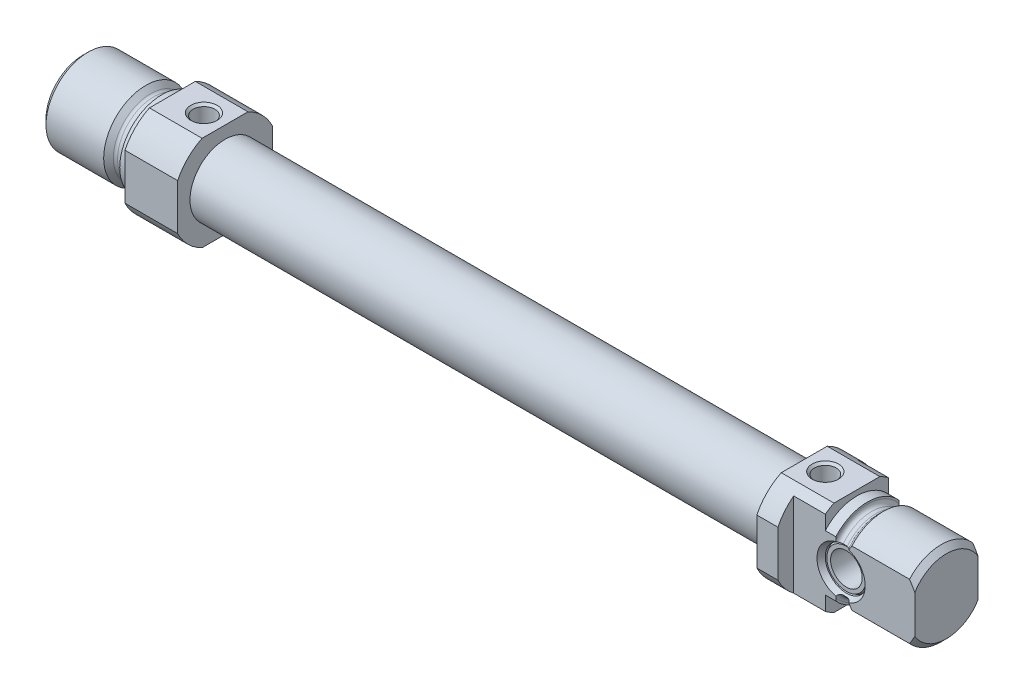
SolidWorks part; units mm, degrees
ref_plane "Front Plane" through (0, 0, 0) normal (0, 0, 1) x (1, 0, 0)
ref_plane "Top Plane" through (0, 0, 0) normal (0, 1, 0) x (1, 0, 0)
ref_plane "Right Plane" through (0, 0, 0) normal (1, 0, 0) x (0, 0, -1)
sketch "Sketch1" plane through (0, 0, 0) normal (0, 0, 1) x (1, 0, 0)
  line L0 (0, 0) -> (0, 7)
  line L1 (0, 7) -> (1, 8)
  line L2 (1, 8) -> (11.95, 8)
  line L3 (11.95, 8) -> (12.8657, 7.0843)
  line L4 (13.4314, 6.85) -> (14.2, 6.85)
  line L5 (15, 7.65) -> (15, 8)
  line L6 (15, 8) -> (17, 8)
  line L7 (17, 8) -> (17, 0)
  line L8 (17, 0) -> (0, 0)
  line L9 (17, 0) -> (0, 0) construction
  arc A0 (12.8657, 7.0843) -> (13.4314, 6.85) centre (13.4314, 7.65) ccw
  arc A1 (14.2, 6.85) -> (15, 7.65) centre (14.2, 7.65) ccw
revolve "Revolve1" add sketch "Sketch1" angle 360 about L9 reverse direction yes
cosmetic thread "Cosmetic Thread1" parameters "D1"=11.87, "D2"=14.16
ref_plane "Plane1" through (21.1, 0, 0) normal (1, 0, 0) x (0, 0, -1)
ref_plane "Plane2" through (9, 0, 0) normal (1, 0, 0) x (0, 0, -1)
ref_plane "Plane3" through (0, -11, 0) normal (0, 1, 0) x (1, 0, 0)
ref_plane "Plane4" through (0, 11, 0) normal (0, 1, 0) x (1, 0, 0)
ref_plane "Plane5" through (0, 0, 0) normal (0, 1, 0) x (1, 0, 0)
ref_plane "Plane6" through (0, 0, 0) normal (0, 1, 0) x (1, 0, 0)
ref_plane "Plane7" through (17, 0, 0) normal (1, 0, 0) x (0, 0, -1)
ref_plane "Plane8" through (17, 0, 0) normal (1, 0, 0) x (0, 0, -1)
ref_plane "Plane9" through (27, 0, 0) normal (1, 0, 0) x (0, 0, -1)
ref_plane "Plane10" through (17, 0, 0) normal (1, 0, 0) x (0, 0, -1)
ref_plane "Plane11" through (17, 0, 0) normal (1, 0, 0) x (0, 0, -1)
sketch "Sketch2" plane through (17, 0, 0) normal (1, 0, 0) x (0, 0, -1)
  line L0 (-4.3589, -9) -> (4.3589, -9)
  line L1 (9, -4.3589) -> (9, 4.3589)
  line L2 (4.3589, 9) -> (-4.3589, 9)
  line L3 (-9, 4.3589) -> (-9, -4.3589)
  arc A0 (-9, -4.3589) -> (-4.3589, -9) centre (0, 0) ccw
  arc A1 (4.3589, -9) -> (9, -4.3589) centre (0, 0) ccw
  arc A2 (9, 4.3589) -> (4.3589, 9) centre (0, 0) ccw
  arc A3 (-4.3589, 9) -> (-9, 4.3589) centre (0, 0) ccw
extrude "Boss-Extrude1" add sketch "Sketch2" along normal blind 10
ref_plane "Plane12" through (23, 0, 0) normal (1, 0, 0) x (0, 0, -1)
ref_plane "Plane13" through (0, 0, 0) normal (0, 0, 1) x (1, 0, 0)
ref_plane "Plane14" through (0, 0, -6.6) normal (0, 0, 1) x (1, 0, 0)
ref_plane "Plane15" through (0, 0, 0) normal (0, 1, 0) x (1, 0, 0)
ref_plane "Plane16" through (0, 7.5, 0) normal (0, 1, 0) x (1, 0, 0)
ref_plane "Plane17" through (0, 0, -6.6) normal (0, 0, 1) x (1, 0, 0)
ref_plane "Plane18" through (0, 0, 0) normal (0, 1, 0) x (1, 0, 0)
ref_plane "Plane19" through (0, 7.5, 0) normal (0, 1, 0) x (1, 0, 0)
ref_plane "Plane20" through (0, 8.4025, -1.4816) normal (0, 0.9848, -0.1736) x (1, 0, 0)
ref_plane "Plane21" through (0, 6.9253, -1.2211) normal (0, 0.9848, -0.1736) x (1, 0, 0)
sketch "Sketch3" plane through (0, 0, 0) normal (0, 0, 1) x (1, 0, 0)
  line L0 (27, 0) -> (27, 6.65)
  line L1 (27, 6.65) -> (137, 6.65)
  line L2 (137, 6.65) -> (137, 0)
  line L3 (137, 0) -> (27, 0)
  line L4 (137, 0) -> (27, 0) construction
revolve "Revolve2" add sketch "Sketch3" angle 360 about L4 reverse direction yes
ref_plane "Plane22" through (137, 0, 0) normal (1, 0, 0) x (0, 0, -1)
sketch "Sketch4" plane through (137, 0, 0) normal (1, 0, 0) x (0, 0, -1)
  line L0 (-9, -9) -> (9, -9)
  line L1 (9, -9) -> (9, 9)
  line L2 (9, 9) -> (-9, 9)
  line L3 (-9, 9) -> (-9, -9)
extrude "Boss-Extrude2" add sketch "Sketch4" along normal blind 10
sketch "Sketch5" plane through (0, 0, 0) normal (0, 0, 1) x (1, 0, 0)
  line L0 (137, 20) -> (137, 10)
  line L1 (137, 10) -> (147, 10)
  line L2 (147, 10) -> (147, 20)
  line L3 (147, 20) -> (137, 20)
  line L4 (147, 0) -> (137, 0) construction
revolve "Cut-Revolve1" cut sketch "Sketch5" angle 360 about L4 reverse direction yes
ref_plane "Plane23" through (139, 0, 0) normal (1, 0, 0) x (0, 0, -1)
ref_plane "Plane24" through (141, 0, 0) normal (1, 0, 0) x (0, 0, -1)
ref_plane "Plane25" through (0, 0, 6.6) normal (0, 0, 1) x (1, 0, 0)
ref_plane "Plane26" through (0, 0, 0) normal (0, 1, 0) x (1, 0, 0)
ref_plane "Plane27" through (0, 7.5, 0) normal (0, 1, 0) x (1, 0, 0)
ref_plane "Plane28" through (0, 8.4025, 1.4816) normal (0, 0.9848, 0.1736) x (1, 0, 0)
ref_plane "Plane29" through (0, 6.9253, 1.2211) normal (0, 0.9848, 0.1736) x (1, 0, 0)
ref_plane "Plane30" through (185, 0, 0) normal (1, 0, 0) x (0, 0, -1)
sketch "Sketch6" plane through (0, 0, 0) normal (0, 0, 1) x (1, 0, 0)
  line L0 (147, 0) -> (147, 8)
  line L1 (147, 8) -> (149, 8)
  line L2 (149, 8) -> (149, 7.65)
  line L3 (149.8, 6.85) -> (150.5686, 6.85)
  line L4 (151.1343, 7.0843) -> (152.05, 8)
  line L5 (152.05, 8) -> (163, 8)
  line L6 (163, 8) -> (164, 7)
  line L7 (164, 7) -> (164, 0)
  line L8 (164, 0) -> (147, 0)
  line L9 (164, 0) -> (147, 0) construction
  arc A0 (149, 7.65) -> (149.8, 6.85) centre (149.8, 7.65) ccw
  arc A1 (150.5686, 6.85) -> (151.1343, 7.0843) centre (150.5686, 7.65) ccw
revolve "Revolve3" add sketch "Sketch6" angle 360 about L9 reverse direction yes
cosmetic thread "Cosmetic Thread2" parameters "D1"=11.87, "D2"=14.16
ref_plane "Plane31" through (175, 0, 0) normal (1, 0, 0) x (0, 0, -1)
ref_plane "Plane32" through (185, 0, 0) normal (1, 0, 0) x (0, 0, -1)
ref_plane "Plane33" through (185, 0, 0) normal (1, 0, 0) x (0, 0, -1)
sketch "Sketch7" plane through (0, 0, 0) normal (0, 1, 0) x (1, 0, 0)
  line L0 (141, 18) -> (141, 6)
  line L1 (141, 6) -> (164, 6)
  line L2 (164, 6) -> (164, -6)
  line L3 (164, -6) -> (141, -6)
  line L4 (141, -6) -> (141, -18)
  line L5 (141, -18) -> (176, -18)
  line L6 (176, -18) -> (176, 18)
  line L7 (176, 18) -> (141, 18)
extrude "Cut-Extrude1" cut sketch "Sketch7" along normal blind 10 and the other way blind 10
ref_plane "Plane34" through (150, 0, 0) normal (1, 0, 0) x (0, 0, -1)
sketch "Sketch8" plane through (150, 0, 0) normal (1, 0, 0) x (0, 0, -1)
  line L0 (-6.2, 0) -> (-6.2, 4.6928)
  line L1 (-6.2, 4.6928) -> (-5, 4)
  line L2 (-5, 4) -> (-4.5, 4)
  line L3 (-4.5, 4) -> (-5, 3.7113)
  line L4 (-5, 3.7113) -> (-5, 3)
  line L5 (-5, 3) -> (5, 3)
  line L6 (5, 3) -> (5, 3.7113)
  line L7 (5, 3.7113) -> (4.5, 4)
  line L8 (4.5, 4) -> (5, 4)
  line L9 (5, 4) -> (6.2, 4.6928)
  line L10 (6.2, 4.6928) -> (6.2, 0)
  line L11 (6.2, 0) -> (-6.2, 0)
  line L12 (5, 0) -> (-6.2, 0) construction
revolve "Cut-Revolve2" cut sketch "Sketch8" angle 360 about L12 reverse direction yes
hole_wizard "Hole1" positions "Sketch10" profile "Sketch9" legacy
sketch "Sketch10" plane through (0, 9, 0) normal (0, 1, 0) x (1, 0, 0)
  point P0 (23, 0)
sketch "Sketch9" plane through (23, 9, 0) normal (1, 0, 0) x (0, 0, 1)
  line L0 (0, 0) -> (0, 9)
  line L1 (0, 9) -> (2.067, 9)
  line L2 (2.067, 9) -> (2.067, 0.433)
  line L3 (2.067, 0.433) -> (2.5, 0)
  line L4 (2.5, 0) -> (0, 0)
  line L5 (0, -6.4453) -> (0, 115.525) construction
  line L6 (-2.067, 0.433) -> (-2.5, 0) construction
  dimension "Diameter" = 4.134
  dimension "Depth" = 9
  dimension "C-Sink Angle" = 90
  dimension "C-Sink Diameter" = 5
cosmetic thread "Cosmetic Thread3" parameters "D1"=7, "D2"=5
hole_wizard "Hole2" positions "Sketch12" profile "Sketch11" legacy
sketch "Sketch12" plane through (0, 9, 0) normal (0, 1, 0) x (1, 0, 0)
  point P0 (141, 0)
sketch "Sketch11" plane through (141, 9, 0) normal (1, 0, 0) x (0, 0, 1)
  line L0 (0, 0) -> (0, 12.1934)
  line L1 (0, 12.1934) -> (2.067, 11)
  line L2 (2.067, 11) -> (2.067, 0.433)
  line L3 (2.067, 0.433) -> (2.5, 0)
  line L4 (2.5, 0) -> (0, 0)
  line L5 (0, -14.3089) -> (0, 102.4216) construction
  line L6 (0, 12.1934) -> (-2.067, 11) construction
  line L7 (-2.067, 0.433) -> (-2.5, 0) construction
  dimension "Diameter" = 4.134
  dimension "Depth" = 11
  dimension "C-Sink Diameter" = 5
  dimension "C-Sink Angle" = 90
  dimension "Drill Angle" = 120
cosmetic thread "Cosmetic Thread4" parameters "D1"=6, "D2"=5
sketch "Sketch13" plane through (0, 0, 0) normal (0, 0, 1) x (1, 0, 0)
  line L0 (-5, 0) -> (-5, 3)
  line L1 (-5, 3) -> (37.3, 3)
  line L2 (37.3, 3) -> (37.3, 6)
  line L3 (37.3, 6) -> (120.3, 6)
  line L4 (120.3, 6) -> (120.3, 0)
  line L5 (120.3, 0) -> (-5, 0)
  line L6 (120.3, 0) -> (-5, 0) construction
revolve "Cut-Revolve3" cut sketch "Sketch13" angle 360 about L6 reverse direction yes
ref_plane "Plane35" through (-5, 0, 0) normal (1, 0, 0) x (0, 0, -1)
ref_plane "Plane36" through (0, 9, 0) normal (0, 1, 0) x (1, 0, 0)
ref_plane "Plane37" through (8, 0, 0) normal (1, 0, 0) x (0, 0, -1)
ref_plane "Plane38" through (0, 0, 0) normal (1, 0, 0) x (0, 0, -1)
ref_plane "Plane39" through (17, 0, 0) normal (1, 0, 0) x (0, 0, -1)
ref_plane "Plane40" through (147, 0, 0) normal (1, 0, 0) x (0, 0, -1)
ref_plane "Plane41" through (17, 0, 0) normal (1, 0, 0) x (0, 0, -1)
ref_plane "Plane42" through (0, 9, 0) normal (0, 1, 0) x (1, 0, 0)
ref_plane "Plane43" through (36.5, 0, 0) normal (1, 0, 0) x (0, 0, -1)
ref_plane "Plane44" through (127.5, 0, 0) normal (1, 0, 0) x (0, 0, -1)
ref_plane "Plane45" through (0, 0, 0) normal (0, 0, 1) x (1, 0, 0)
ref_plane "Plane46" through (17, 0, 0) normal (1, 0, 0) x (0, 0, -1)
ref_plane "Plane47" through (0, 9, 0) normal (0, 1, 0) x (1, 0, 0)
ref_plane "Plane48" through (3, 0, 0) normal (1, 0, 0) x (0, 0, -1)
ref_plane "Plane49" through (0, 9, 0) normal (0, 1, 0) x (1, 0, 0)
ref_plane "FDT_FRONT XY" through (17, 0, 0) normal (1, 0, 0) x (0, 0, -1)
ref_plane "FDT_FRONT XZ" through (0, 0, 0) normal (0, -1, 0) x (-1, 0, 0)
ref_plane "FDT_FRONT YZ" through (0, 0, 0) normal (0, 0, -1) x (-1, 0, 0)
ref_axis "FDT_FRONT X" through (17, 0, 80.9) along (0, 0, -1)
ref_axis "FDT_FRONT Y" through (17, -50, 0) along (0, 1, 0)
ref_axis "FDT_FRONT Z" through (80.9, 0, 0) along (-1, 0, 0)
sketch3d "FDT_FRONT"
  point P0 (17, 0, 0)
ref_plane "FDT_QSFRONT XY" through (0, 9, 0) normal (0, 1, 0) x (1, 0, 0)
ref_plane "FDT_QSFRONT XZ" through (23, 0, 0) normal (-1, 0, 0) x (0, 0, 1)
ref_plane "FDT_QSFRONT YZ" through (0, 0, 0) normal (0, 0, 1) x (1, 0, 0)
ref_axis "FDT_QSFRONT X" through (23, 9, -50) along (0, 0, 1)
ref_axis "FDT_QSFRONT Y" through (-80.9, 9, 0) along (1, 0, 0)
ref_axis "FDT_QSFRONT Z" through (23, 50, 0) along (0, -1, 0)
sketch3d "FDT_QSFRONT"
  point P0 (23, 9, 0)
ref_plane "FDT_QSREAR XY" through (0, 9, 0) normal (0, 1, 0) x (1, 0, 0)
ref_plane "FDT_QSREAR XZ" through (141, 0, 0) normal (-1, 0, 0) x (0, 0, 1)
ref_plane "FDT_QSREAR YZ" through (0, 0, 0) normal (0, 0, 1) x (1, 0, 0)
ref_axis "FDT_QSREAR X" through (141, 9, -50) along (0, 0, 1)
ref_axis "FDT_QSREAR Y" through (-80.9, 9, 0) along (1, 0, 0)
ref_axis "FDT_QSREAR Z" through (141, 50, 0) along (0, -1, 0)
sketch3d "FDT_QSREAR"
  point P0 (141, 9, 0)
ref_plane "FDT_REAR XY" through (147, 0, 0) normal (-1, 0, 0) x (0, 0, 1)
ref_plane "FDT_REAR XZ" through (0, 0, 0) normal (0, 1, 0) x (1, 0, 0)
ref_plane "FDT_REAR YZ" through (0, 0, 0) normal (0, 0, -1) x (-1, 0, 0)
ref_axis "FDT_REAR X" through (147, 0, 80.9) along (0, 0, -1)
ref_axis "FDT_REAR Y" through (147, 50, 0) along (0, -1, 0)
ref_axis "FDT_REAR Z" through (-80.9, 0, 0) along (1, 0, 0)
sketch3d "FDT_REAR"
  point P0 (147, 0, 0)
ref_plane "FDT_SMBR1 XY" through (36.5, 0, 0) normal (-1, 0, 0) x (0, 0, 1)
ref_plane "FDT_SMBR1 XZ" through (0, 0, 0) normal (0, -1, 0) x (-1, 0, 0)
ref_plane "FDT_SMBR1 YZ" through (0, 0, 0) normal (0, 0, 1) x (1, 0, 0)
ref_axis "FDT_SMBR1 X" through (36.5, 0, -80.9) along (0, 0, 1)
ref_axis "FDT_SMBR1 Y" through (36.5, -50, 0) along (0, 1, 0)
ref_axis "FDT_SMBR1 Z" through (-80.9, 0, 0) along (1, 0, 0)
sketch3d "FDT_SMBR1"
  point P0 (36.5, 0, 0)
ref_plane "FDT_SMBR2 XY" through (127.5, 0, 0) normal (-1, 0, 0) x (0, 0, 1)
ref_plane "FDT_SMBR2 XZ" through (0, 0, 0) normal (0, -1, 0) x (-1, 0, 0)
ref_plane "FDT_SMBR2 YZ" through (0, 0, 0) normal (0, 0, 1) x (1, 0, 0)
ref_axis "FDT_SMBR2 X" through (127.5, 0, -80.9) along (0, 0, 1)
ref_axis "FDT_SMBR2 Y" through (127.5, -50, 0) along (0, 1, 0)
ref_axis "FDT_SMBR2 Z" through (-80.9, 0, 0) along (1, 0, 0)
sketch3d "FDT_SMBR2"
  point P0 (127.5, 0, 0)
ref_plane "FDT_SWIVELAXIS XY" through (0, 0, 0) normal (0, 0, 1) x (1, 0, 0)
ref_plane "FDT_SWIVELAXIS XZ" through (0, 0, 0) normal (0, -1, 0) x (-1, 0, 0)
ref_plane "FDT_SWIVELAXIS YZ" through (150, 0, 0) normal (1, 0, 0) x (0, 0, -1)
ref_axis "FDT_SWIVELAXIS X" through (-80.9, 0, 0) along (1, 0, 0)
ref_axis "FDT_SWIVELAXIS Y" through (150, -50, 0) along (0, 1, 0)
ref_axis "FDT_SWIVELAXIS Z" through (150, 0, 80.9) along (0, 0, -1)
sketch3d "FDT_SWIVELAXIS"
  point P0 (150, 0, 0)
ref_plane "NUT XY" through (8, 0, 0) normal (1, 0, 0) x (0, 0, -1)
ref_plane "NUT XZ" through (0, 0, 0) normal (0, -1, 0) x (-1, 0, 0)
ref_plane "NUT YZ" through (0, 0, 0) normal (0, 0, -1) x (-1, 0, 0)
ref_axis "NUT X" through (8, 0, 80.9) along (0, 0, -1)
ref_axis "NUT Y" through (8, -50, 0) along (0, 1, 0)
ref_axis "NUT Z" through (80.9, 0, 0) along (-1, 0, 0)
sketch3d "NUT"
  point P0 (8, 0, 0)
ref_plane "ZR XY" through (0, 0, 0) normal (-1, 0, 0) x (0, 0, 1)
ref_plane "ZR XZ" through (0, 0, 0) normal (0, 1, 0) x (1, 0, 0)
ref_plane "ZR YZ" through (0, 0, 0) normal (0, 0, -1) x (-1, 0, 0)
ref_axis "ZR X" through (0, 0, 80.9) along (0, 0, -1)
ref_axis "ZR Y" through (0, 50, 0) along (0, -1, 0)
ref_axis "ZR Z" through (-80.9, 0, 0) along (1, 0, 0)
sketch3d "ZR"
  point P0 (0, 0, 0)
ref_plane "ZYL XY" through (17, 0, 0) normal (1, 0, 0) x (0, 0, -1)
ref_plane "ZYL XZ" through (0, 0, 0) normal (0, -1, 0) x (-1, 0, 0)
ref_plane "ZYL YZ" through (0, 0, 0) normal (0, 0, -1) x (-1, 0, 0)
ref_axis "ZYL X" through (17, 0, 80.9) along (0, 0, -1)
ref_axis "ZYL Y" through (17, -50, 0) along (0, 1, 0)
ref_axis "ZYL Z" through (80.9, 0, 0) along (-1, 0, 0)
sketch3d "ZYL"
  point P0 (17, 0, 0)
